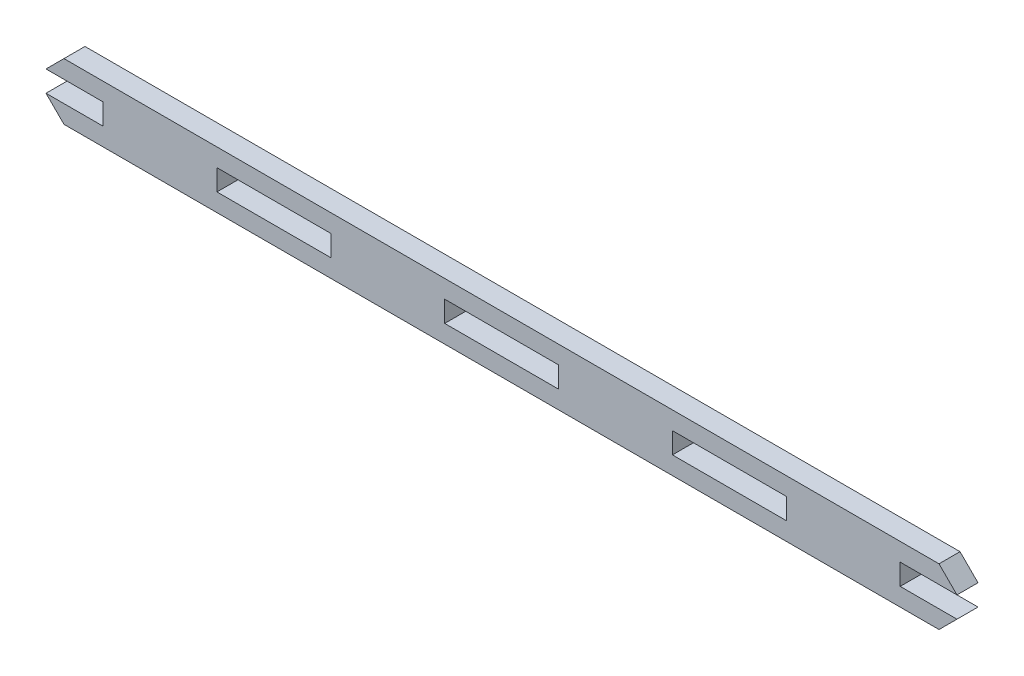
SolidWorks part; units mm, degrees
ref_plane "Front Plane" through (0, 0, 0) normal (0, 0, 1) x (1, 0, 0)
ref_plane "Top Plane" through (0, 0, 0) normal (0, 1, 0) x (1, 0, 0)
ref_plane "Right Plane" through (0, 0, 0) normal (1, 0, 0) x (0, 0, -1)
sketch "Sketch2" plane through (0, 0, 0) normal (0, 0, 1) x (1, 0, 0)
  line L5 (55.6137, 15.146) -> (286.1537, 15.146)
  line L35 (170.8837, 15.146) -> (170.961, 0.146) construction
  line L36 (215.9223, 10.416) -> (215.9223, 4.876)
  line L37 (215.9223, 10.416) -> (245.9223, 10.416)
  line L38 (245.9223, 10.416) -> (245.9223, 4.876)
  line L40 (55.6137, 0.146) -> (286.1537, 0.146)
  line L42 (155.9223, 10.416) -> (185.9223, 10.416)
  line L43 (155.9223, 10.416) -> (155.9223, 4.876)
  line L44 (155.9223, 4.876) -> (185.9223, 4.876)
  line L45 (185.9223, 10.416) -> (185.9223, 4.876)
  line L57 (50.8837, 10.416) -> (55.6137, 15.146)
  line L58 (50.8837, 4.876) -> (55.6137, 0.146)
  line L59 (286.1537, 0.146) -> (290.8837, 4.876)
  line L60 (286.1537, 15.146) -> (290.8837, 10.416)
  line L61 (215.9223, 4.876) -> (245.9223, 4.876)
  line L62 (95.9223, 10.416) -> (95.9223, 4.876)
  line L63 (95.9223, 10.416) -> (125.9223, 10.416)
  line L64 (125.9223, 10.416) -> (125.9223, 4.876)
  line L65 (95.9223, 4.876) -> (125.9223, 4.876)
  line L67 (50.8837, 4.876) -> (65.9223, 4.876)
  line L69 (50.8837, 10.416) -> (65.9223, 10.416)
  line L70 (65.9223, 4.876) -> (65.9223, 10.416)
  line L71 (290.8837, 4.876) -> (275.9223, 4.876)
  line L73 (290.8837, 10.416) -> (275.9223, 10.416)
  line L74 (275.9223, 4.876) -> (275.9223, 10.416)
  point P0 (50.8837, 15.146)
  point P1 (290.8837, 0.146)
  point P2 (50.8837, 0.146)
  point P3 (290.8837, 15.146)
  point P12 (170.9223, 7.646)
  point P31 (170.8837, 0.146)
  dimension "D1" = 240
  dimension "D2" = 15
  dimension "D3" = 4.73
  dimension "D4" = 5.54
  dimension "D5" = 30
  dimension "D6" = 15
  dimension "D8" = 2
  dimension "D9" = 30
  dimension "D10" = 30
  dimension "D11" = 30
  dimension "D12" = 30
  dimension "D7" = 2
extrude "Boss-Extrude1" add sketch "Sketch2" along normal blind 5.54
